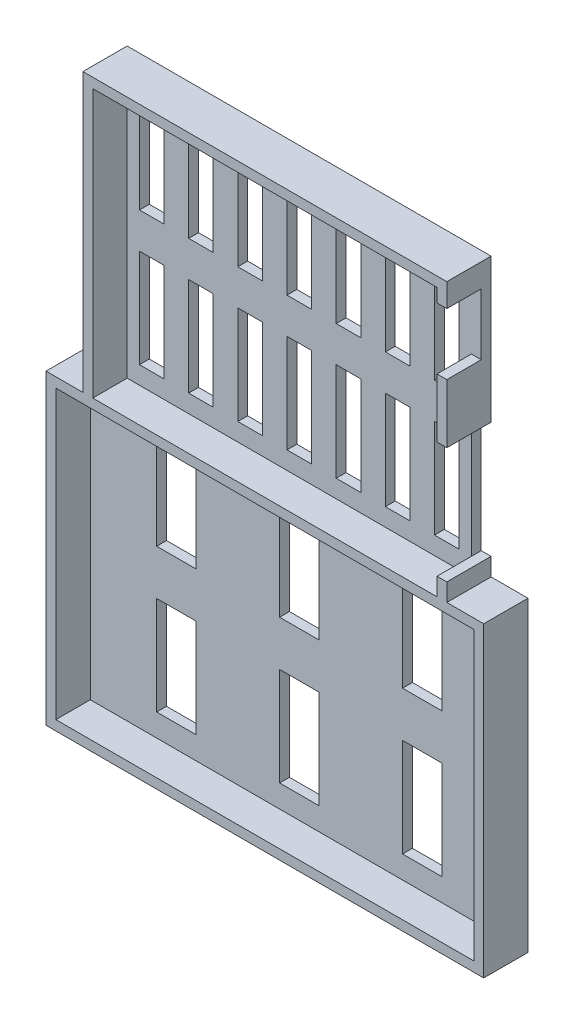
SolidWorks part; units mm, degrees
ref_plane "Front Plane" through (0, 0, 0) normal (0, 0, 1) x (1, 0, 0)
ref_plane "Top Plane" through (0, 0, 0) normal (0, 1, 0) x (1, 0, 0)
ref_plane "Right Plane" through (0, 0, 0) normal (1, 0, 0) x (0, 0, -1)
sketch "Sketch1" plane through (0, 0, 0) normal (0, 0, 1) x (1, 0, 0)
  line L0 (-37, 29.25) -> (37, 29.25)
  line L1 (-35, 27.25) -> (35, 27.25)
  line L2 (-35, 27.25) -> (-35, -27.25)
  line L3 (-35, -27.25) -> (35, -27.25)
  line L4 (35, 27.25) -> (35, -27.25)
  line L5 (-35, 27.25) -> (35, -27.25) construction
  line L6 (-35, -27.25) -> (35, 27.25) construction
  line L7 (37, 29.25) -> (37, -29.25)
  line L8 (-37, -29.25) -> (37, -29.25)
  line L9 (-37, 29.25) -> (-37, -29.25)
  line L10 (0, 27.25) -> (0, 0)
  line L11 (7.5, 23.625) -> (7.5, 3.625)
  line L12 (-2.5, 23.625) -> (2.5, 23.625)
  line L13 (-2.5, 23.625) -> (-2.5, 3.625)
  line L14 (-2.5, 3.625) -> (2.5, 3.625)
  line L15 (2.5, 23.625) -> (2.5, 3.625)
  line L16 (-2.5, 23.625) -> (2.5, 3.625) construction
  line L17 (-2.5, 3.625) -> (2.5, 23.625) construction
  line L18 (7.5, 23.625) -> (12.5, 23.625)
  line L19 (12.5, 23.625) -> (12.5, 3.625)
  line L20 (7.5, 3.625) -> (12.5, 3.625)
  line L21 (17.5, 23.625) -> (17.5, 3.625)
  line L22 (17.5, 23.625) -> (22.5, 23.625)
  line L23 (22.5, 23.625) -> (22.5, 3.625)
  line L24 (17.5, 3.625) -> (22.5, 3.625)
  line L25 (27.5, 23.625) -> (27.5, 3.625)
  line L26 (27.5, 23.625) -> (32.5, 23.625)
  line L27 (32.5, 23.625) -> (32.5, 3.625)
  line L28 (27.5, 3.625) -> (32.5, 3.625)
  line L29 (-12.5, 23.625) -> (-12.5, 3.625)
  line L30 (-12.5, 23.625) -> (-7.5, 23.625)
  line L31 (-7.5, 23.625) -> (-7.5, 3.625)
  line L32 (-12.5, 3.625) -> (-7.5, 3.625)
  line L33 (-22.5, 23.625) -> (-22.5, 3.625)
  line L34 (-22.5, 23.625) -> (-17.5, 23.625)
  line L35 (-17.5, 23.625) -> (-17.5, 3.625)
  line L36 (-22.5, 3.625) -> (-17.5, 3.625)
  line L37 (-32.5, 23.625) -> (-32.5, 3.625)
  line L38 (-32.5, 23.625) -> (-27.5, 23.625)
  line L39 (-27.5, 23.625) -> (-27.5, 3.625)
  line L40 (-32.5, 3.625) -> (-27.5, 3.625)
  line L41 (-27.5, 0) -> (16.7782, 0)
  line L42 (-2.5, -3.625) -> (2.5, -23.625) construction
  line L43 (-2.5, -23.625) -> (2.5, -3.625) construction
  line L44 (-32.5, -3.625) -> (-27.5, -3.625)
  line L45 (-27.5, -23.625) -> (-27.5, -3.625)
  line L46 (-32.5, -23.625) -> (-27.5, -23.625)
  line L47 (-32.5, -23.625) -> (-32.5, -3.625)
  line L48 (-22.5, -3.625) -> (-17.5, -3.625)
  line L49 (-17.5, -23.625) -> (-17.5, -3.625)
  line L50 (-22.5, -23.625) -> (-17.5, -23.625)
  line L51 (-22.5, -23.625) -> (-22.5, -3.625)
  line L52 (-12.5, -3.625) -> (-7.5, -3.625)
  line L53 (-7.5, -23.625) -> (-7.5, -3.625)
  line L54 (-12.5, -23.625) -> (-7.5, -23.625)
  line L55 (-12.5, -23.625) -> (-12.5, -3.625)
  line L56 (27.5, -3.625) -> (32.5, -3.625)
  line L57 (32.5, -23.625) -> (32.5, -3.625)
  line L58 (27.5, -23.625) -> (32.5, -23.625)
  line L59 (27.5, -23.625) -> (27.5, -3.625)
  line L60 (17.5, -3.625) -> (22.5, -3.625)
  line L61 (22.5, -23.625) -> (22.5, -3.625)
  line L62 (17.5, -23.625) -> (22.5, -23.625)
  line L63 (17.5, -23.625) -> (17.5, -3.625)
  line L64 (7.5, -3.625) -> (12.5, -3.625)
  line L65 (12.5, -23.625) -> (12.5, -3.625)
  line L66 (7.5, -23.625) -> (12.5, -23.625)
  line L67 (2.5, -23.625) -> (2.5, -3.625)
  line L68 (-2.5, -3.625) -> (2.5, -3.625)
  line L69 (-2.5, -23.625) -> (-2.5, -3.625)
  line L70 (-2.5, -23.625) -> (2.5, -23.625)
  line L71 (7.5, -23.625) -> (7.5, -3.625)
  line L72 (0, -29.25) -> (0, -58.4405)
  line L73 (-44.5, -27.25) -> (-44.5, -89.631)
  line L74 (-42.5, -29.25) -> (42.5, -29.25)
  line L75 (-42.5, -29.25) -> (-42.5, -87.631)
  line L76 (-42.5, -87.631) -> (42.5, -87.631)
  line L77 (42.5, -29.25) -> (42.5, -87.631)
  line L78 (-42.5, -29.25) -> (42.5, -87.631) construction
  line L79 (-42.5, -87.631) -> (42.5, -29.25) construction
  line L80 (-44.5, -89.631) -> (44.5, -89.631)
  line L81 (44.5, -27.25) -> (44.5, -89.631)
  line L83 (-44.5, -27.25) -> (44.5, -27.25) construction
  line L84 (-44.5, -27.25) -> (-37, -27.25)
  line L85 (44.5, -27.25) -> (37, -27.25)
  line L86 (35, 0) -> (37, 0)
  line L87 (35, -27.25) -> (37, -27.25)
  line L88 (29, -33.8453) -> (29, -53.8453)
  line L89 (-4, -33.8453) -> (4, -33.8453)
  line L90 (-4, -33.8453) -> (-4, -53.8453)
  line L91 (-4, -53.8453) -> (4, -53.8453)
  line L92 (4, -33.8453) -> (4, -53.8453)
  line L93 (-4, -33.8453) -> (4, -53.8453) construction
  line L94 (-4, -53.8453) -> (4, -33.8453) construction
  line L95 (21, -33.8453) -> (21, -53.8453)
  line L96 (21, -33.8453) -> (29, -33.8453)
  line L97 (21, -53.8453) -> (29, -53.8453)
  line L98 (-21, -33.8453) -> (-21, -53.8453)
  line L99 (-29, -33.8453) -> (-29, -53.8453)
  line L100 (-29, -33.8453) -> (-21, -33.8453)
  line L101 (-29, -53.8453) -> (-21, -53.8453)
  line L102 (-13.6992, -58.4405) -> (9.9002, -58.4405)
  line L103 (-4, -63.0358) -> (4, -83.0358) construction
  line L104 (-4, -83.0358) -> (4, -63.0358) construction
  line L105 (-29, -63.0358) -> (-21, -63.0358)
  line L106 (-29, -83.0358) -> (-21, -83.0358)
  line L107 (-29, -83.0358) -> (-29, -63.0358)
  line L108 (-21, -83.0358) -> (-21, -63.0358)
  line L109 (21, -63.0358) -> (29, -63.0358)
  line L110 (21, -83.0358) -> (29, -83.0358)
  line L111 (21, -83.0358) -> (21, -63.0358)
  line L112 (4, -83.0358) -> (4, -63.0358)
  line L113 (-4, -63.0358) -> (4, -63.0358)
  line L114 (-4, -83.0358) -> (-4, -63.0358)
  line L115 (-4, -83.0358) -> (4, -83.0358)
  line L116 (29, -83.0358) -> (29, -63.0358)
  line L117 (35, -23.625) -> (37, -23.625)
  line L118 (35, 24.5) -> (37, 24.5)
  line L120 (35, 12) -> (37, 12)
  point P0 (0, 0)
  point P12 (0, 13.625)
  point P71 (0, -13.625)
  point P74 (0, -58.4405)
  point P87 (0, -43.8453)
  point P114 (0, -73.0358)
  dimension "D1" = 70
  dimension "D2" = 54.5
  dimension "D4" = 20
  dimension "D5" = 5
  dimension "D8" = 20
  dimension "D9" = 85
  dimension "D11" = 8
  dimension "D3" = 2
  dimension "D10" = 2
  dimension "D6" = 4
  dimension "D7" = 4
  dimension "D12" = 2
  dimension "D13" = 2
extrude "Boss-Extrude1" add sketch "Sketch1" along normal blind 2 contours L75 L76 L8 L74 | L77 L74 L8 L76 | L12 L15 L14 L13 L1 L2 L3 L4 L70 L69 L68 L67 L40 L37 L38 L39 L36 L33 L34 L35 L32 L29 L30 L31 L28 L25 L26 L27 L24 L21 L22 L23 L20 | L4 L120 L7 L118 region at (36, 18.25, 0) region at (-18.5, -30.2812, 0) region at (34.1129, 18.25, 0)
extrude "Boss-Extrude2" add sketch "Sketch1<3>" along normal blind 9 contours L0 L9 L8 L7 L1 L4 L3 L2 | L81 L85 L7 L74 L77 L76 L75 L9 L84 L73 L80 | L117 L4 L87 L7 | L120 L4 L86 L7 region at (0, 28.3067, 0) region at (-38.0868, -28.25, 0) region at (36, 6, 0) region at (36, -25.4375, 0)
sketch "Sketch1<3>" plane through (0, 0, 0) normal (0, 0, 1) x (1, 0, 0) same geometry as "Sketch1"
